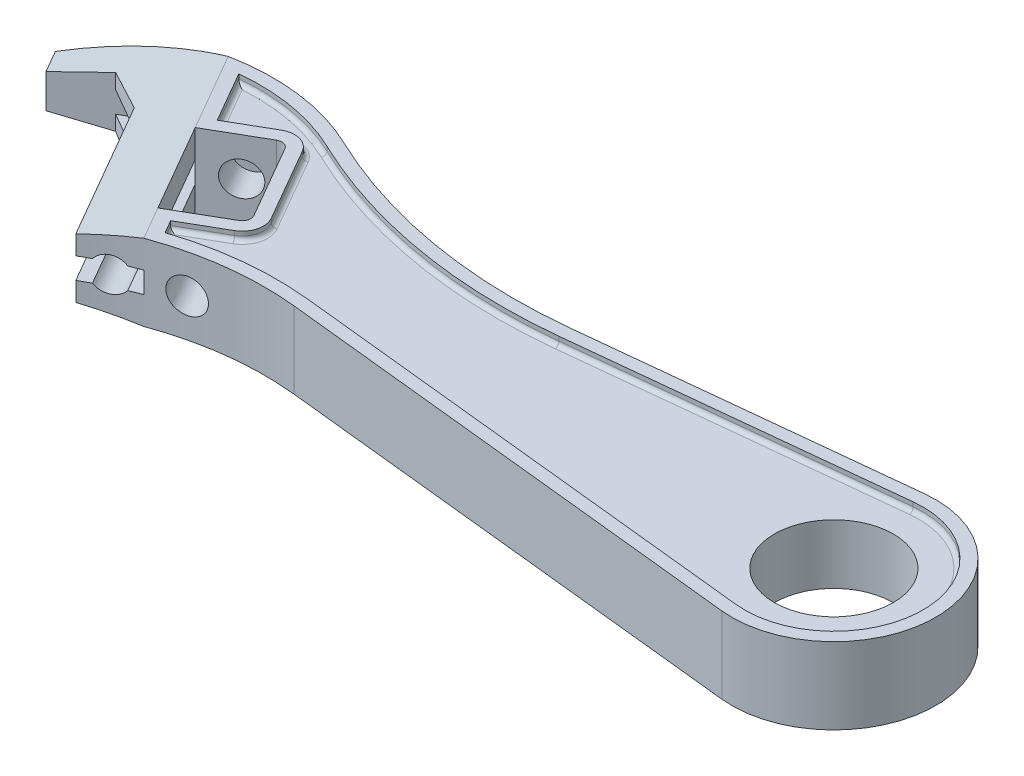
SolidWorks part; units mm, degrees
material "AISI 4340 Steel, annealed"
ref_plane "Front Plane" through (0, 0, 0) normal (0, 0, 1) x (1, 0, 0)
ref_plane "Top Plane" through (0, 0, 0) normal (0, 1, 0) x (1, 0, 0)
ref_plane "Right Plane" through (0, 0, 0) normal (1, 0, 0) x (0, 0, -1)
sketch "Sketch2" plane through (0, 0, 0) normal (0, 1, 0) x (1, 0, 0)
  line L0 (-38.9855, 7.9686) -> (-1.2543, 11.9343)
  line L1 (-1.2543, -11.9343) -> (-57.5473, -6.0176)
  line L2 (-78.7058, -10.515) -> (-88.1077, 5.7696)
  line L3 (-88.1077, 5.7696) -> (-93.3038, 8.7696)
  line L4 (-93.3038, 8.7696) -> (-98.5, 5.7696)
  line L5 (-98.5, 5.7696) -> (-100, 8.3677)
  line L6 (-81.5096, 6.3414) -> (-75.5096, -4.0509)
  line L7 (-75.5096, -4.0509) -> (-69.4474, -0.5509)
  line L8 (-69.0814, 0.8151) -> (-74.0814, 9.4754)
  line L9 (-75.4474, 9.8414) -> (-81.5096, 6.3414)
  line L10 (0, 0) -> (-26.7907, 0) construction
  line L11 (-109.0954, 16) -> (-67.1113, 16) construction
  circle A0 centre (0, 0) radius 7
  arc A1 (-1.2543, 11.9343) -> (-1.2543, -11.9343) centre (0, 0) cw
  arc A2 (-57.5473, -6.0176) -> (-78.7058, -10.515) centre (-61.2058, -40.8259) ccw
  arc A5 (-100, 8.3677) -> (-71.2058, 13.5411) centre (-82.0177, -9) cw
  arc A6 (-38.9855, 7.9686) -> (-71.2058, 13.5411) centre (-45.2572, 67.6399) cw
  arc A7 (-69.4474, -0.5509) -> (-69.0814, 0.8151) centre (-69.9474, 0.3151) ccw
  arc A8 (-74.0814, 9.4754) -> (-75.4474, 9.8414) centre (-74.9474, 8.9754) ccw
  point P23 (12, 0)
  dimension "D1" = 14
  dimension "D10" = 25
  dimension "D15" = 35
  dimension "D16" = 60
  dimension "D19" = 1
  dimension "D2" = 5
  dimension "D4" = 3
  dimension "D5" = 60
  dimension "D7" = 12
  dimension "D11" = 6
  dimension "D12" = 6
  dimension "D13" = 12
  dimension "D14" = 8
  dimension "D9" = 150
  dimension "D17" = 4
  dimension "D18" = 16
  dimension "D8" = 8
extrude "Boss-Extrude1" add sketch "Sketch2" along normal mid plane 9
sketch "Sketch3" plane through (-23.1233, 0, -40.0507) normal (0.5, 0, 0.866) x (0.866, 0, -0.5)
  line L0 (-52.8462, 4.5) -> (-7.0534, 4.5) construction
  line L1 (-82.4187, 1.25) -> (-59.4187, 1.25) construction
  line L2 (-82.4187, 1.25) -> (-82.4187, -1.25)
  line L3 (-82.4187, -1.25) -> (-59.4187, -1.25) construction
  line L4 (-59.4187, 1.25) -> (-59.4187, -1.25) construction
  line L5 (-59.4187, 4.5) -> (-59.4187, -4.5) construction
  line L6 (-59.4187, 4.5) -> (-59.4187, -4.5) construction
  line L7 (-60.4187, -4.5) -> (-67.4187, -4.5) construction
  line L8 (-82.4187, 4.5) -> (-82.4187, -4.5) construction
  line L9 (-67.4187, 1.25) -> (-67.4187, -1.25) construction
  line L10 (-67.4187, 4.5) -> (-67.4187, -4.5) construction
  line L11 (-67.4187, 0) -> (-59.4187, 0) construction
  line L12 (-82.4187, 1.25) -> (-71.98, 1.25)
  line L18 (-71.98, -1.25) -> (-82.4187, -1.25)
  line L19 (-82.4187, 2) -> (-67.4187, 4.5)
  line L20 (-52.8462, 4.5) -> (-73.4187, 4.5) construction
  line L21 (-67.4187, 4.5) -> (-82.4187, 4.5)
  line L22 (-82.4187, 4.5) -> (-82.4187, 2)
  line L23 (-82.4187, 0) -> (-63.4187, 0) construction
  line L24 (-67.4187, -4.5) -> (-82.4187, -4.5)
  line L25 (-82.4187, -2) -> (-67.4187, -4.5)
  line L26 (-82.4187, -4.5) -> (-82.4187, -2)
  line L27 (-68.8575, 1.25) -> (-64.98, 1.25)
  line L28 (-68.8575, -1.25) -> (-64.98, -1.25)
  circle A0 centre (-63.4187, 0) radius 2
  arc A1 (-71.98, 1.25) -> (-71.98, -1.25) centre (-70.4187, 0) cw
  point P12 (-59.4187, 0)
  point P13 (-59.4187, 0)
  point P15 (-67.4187, 0)
  point P27 (-63.4187, 0)
  line M10 (-67.4187, 4.5) -> (-67.4187, -4.5)
  dimension "D2" = 4
  dimension "D3" = 2
  dimension "D1" = 2.5
  dimension "D4" = 12
  dimension "D5" = 2.5
extrude "Cut-Extrude1" cut sketch "Sketch3" against normal up to surface (8 mm away) and the other way through all contours L12 L2 L18 M10 | L27 A1 L28 M10 region at (-88.1199, 0, -2.525) region at (-82.0091, 0, -6.053) up to face at (-95.9019, 0, -7.2696)
extrude "Cut-Extrude4" cut sketch "Sketch3<5>" along normal through all and the other way blind 4 contours A0 region at (-78.0455, 0, -8.3414)
sketch "Sketch3<5>" plane through (-23.1233, 0, -40.0507) normal (0.5, 0, 0.866) x (0.866, 0, -0.5) same geometry as "Sketch3"
extrude "Cut-Extrude2" cut sketch "Sketch3<3>" against normal through all both and the other way through all contours L21 L22 L19 | L26 L24 L25 region at (-90.1699, 3.6667, -1.3414) region at (-90.1699, -3.6667, -1.3414)
sketch "Sketch3<3>" plane through (-23.1233, 0, -40.0507) normal (0.5, 0, 0.866) x (0.866, 0, -0.5) same geometry as "Sketch3"
sketch "Sketch4" plane through (0, 4.5, 0) normal (0, 1, 0) x (1, 0, 0)
  line L7 (-84.417, 14.3772) -> (-80.9606, 8.3904)
  line L8 (-84.417, 14.3772) -> (-80.9606, 8.3904)
  line L9 (-80.9606, 8.3904) -> (-76.1974, 11.1404)
  line L10 (-80.9606, 8.3904) -> (-76.1974, 11.1404)
  line L14 (-72.7824, 10.2254) -> (-67.7824, 1.5651)
  line L15 (-68.6974, -1.85) -> (-73.4606, -4.6)
  line L16 (-57.3905, -4.5259) -> (-1.0975, -10.4425)
  line L17 (-1.0975, 10.4425) -> (-38.8287, 6.4768)
  line L18 (-72.7824, 10.2254) -> (-67.7824, 1.5651)
  line L19 (-68.6974, -1.85) -> (-73.4606, -4.6)
  line L20 (-57.3905, -4.5259) -> (-1.0975, -10.4425)
  line L21 (-1.0975, 10.4425) -> (-38.8287, 6.4768)
  line L26 (-73.4606, -4.6) -> (-72.5712, -6.1405)
  line L27 (-73.4606, -4.6) -> (-72.5712, -6.1405)
  arc A6 (-71.8545, 12.1887) -> (-84.417, 14.3772) centre (-82.0177, -9) ccw
  arc A8 (-71.8545, 12.1887) -> (-84.417, 14.3772) centre (-82.0177, -9) ccw
  arc A9 (-57.3905, -4.5259) -> (-72.5712, -6.1405) centre (-61.2058, -40.8259) ccw
  arc A10 (-1.0975, -10.4425) -> (-1.0975, 10.4425) centre (0, 0) ccw
  arc A11 (-71.8545, 12.1887) -> (-38.8287, 6.4768) centre (-45.2572, 67.6399) ccw
  arc A13 (-57.3905, -4.5259) -> (-72.5712, -6.1405) centre (-61.2058, -40.8259) ccw
  arc A14 (-1.0975, -10.4425) -> (-1.0975, 10.4425) centre (0, 0) ccw
  arc A15 (-71.8545, 12.1887) -> (-38.8287, 6.4768) centre (-45.2572, 67.6399) ccw
  arc A16 (-68.6974, -1.85) -> (-67.7824, 1.5651) centre (-69.9474, 0.3151) ccw
  arc A17 (-68.6974, -1.85) -> (-67.7824, 1.5651) centre (-69.9474, 0.3151) ccw
  arc A18 (-72.7824, 10.2254) -> (-76.1974, 11.1404) centre (-74.9474, 8.9754) ccw
  arc A19 (-72.7824, 10.2254) -> (-76.1974, 11.1404) centre (-74.9474, 8.9754) ccw
  dimension "D1" = 1.5
extrude "Cut-Extrude3" cut sketch "Sketch4" against normal blind 1
fillet "Fillet1" radius 0.5 13 edges at (-65.0662, 3.5, 4.5306) (-29.244, 3.5, 7.4842) (10.5, 3.5, 0) (-77.9845, 3.5, -14.1513) (-55.7382, 3.5, -7.0395) (-78.579, 3.5, -9.7654) (-74.3004, 3.5, -11.3902) (-70.2824, 3.5, -5.8952) (-71.079, 3.5, 3.225) (-82.6888, 3.5, -11.3838) (-19.9631, 3.5, -8.4596) (-67.5326, 3.5, 0.3319) (-73.0159, 3.5, 5.3702)
mirror "Mirror1" about plane through (0, 0, 0) normal (0, 1, 0) of "Fillet1", "Cut-Extrude3"
equation "\"A\"= 112"
equation "\"D3@Sketch2\"= \"A\""
